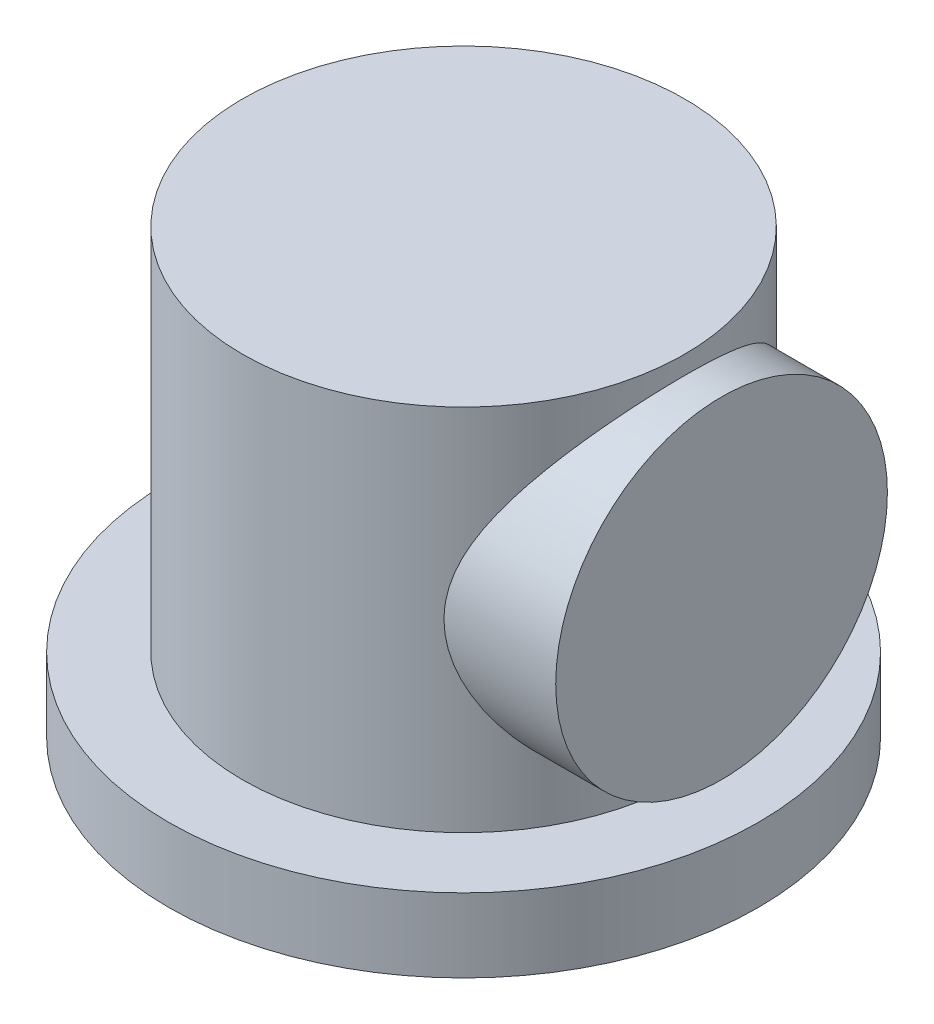
SolidWorks part; units mm, degrees
ref_plane "Front Plane" through (0, 0, 0) normal (0, 0, 1) x (1, 0, 0)
ref_plane "Top Plane" through (0, 0, 0) normal (0, 1, 0) x (1, 0, 0)
ref_plane "Right Plane" through (0, 0, 0) normal (1, 0, 0) x (0, 0, -1)
sketch "Sketch1" plane through (0, 0, 0) normal (0, 1, 0) x (1, 0, 0)
  circle A0 centre (0, 0) radius 50.8
  circle A1 centre (0, 0) radius 38.1
  dimension "D1" = 101.6
  dimension "D2" = 76.2
extrude "Boss-Extrude1" add sketch "Sketch1" along normal blind 12.7 contours A1 | A0 A1 region at (-49.3632, 0, 0) region at (0, 0, 0)
extrude "Boss-Extrude2" add sketch "Sketch1<3>" along normal blind 63.5 from surface contours A1 region at (0, 0, 0) starting at face at (0, 12.7, 50.8)
sketch "Sketch1<3>" plane through (0, 0, 0) normal (0, 1, 0) x (1, 0, 0) same geometry as "Sketch1"
sketch "Sketch2" plane through (0, 0, 0) normal (1, 0, 0) x (0, 0, -1)
  line L0 (50.8, 12.7) -> (-50.8, 12.7) construction
  circle A0 centre (0, 44.45) radius 28.575
  point P2 (0, 0)
  dimension "D1" = 57.15
  dimension "D2" = 31.75
extrude "Boss-Extrude3" add sketch "Sketch2" along normal blind 44.45
